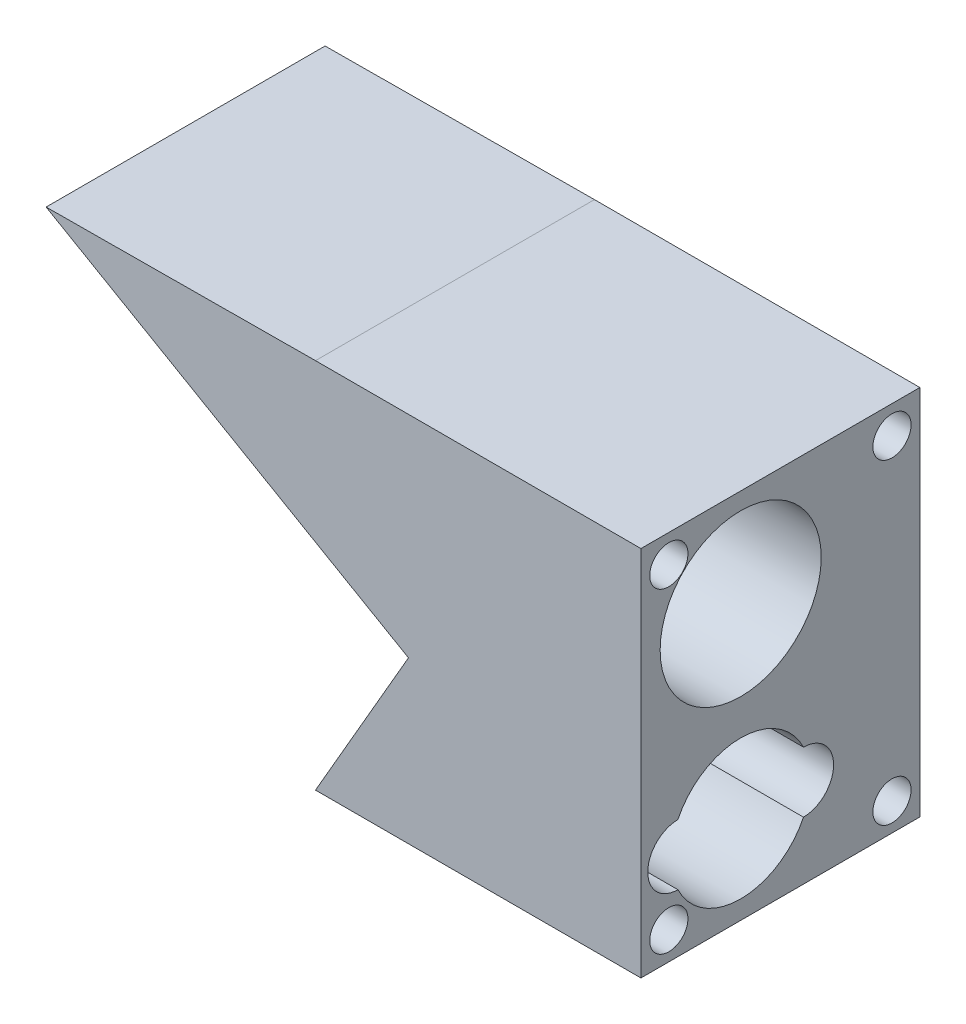
SolidWorks part; units mm, degrees
ref_plane "Front Plane" through (0, 0, 0) normal (0, 0, 1) x (1, 0, 0)
ref_plane "Top Plane" through (0, 0, 0) normal (0, 1, 0) x (1, 0, 0)
ref_plane "Right Plane" through (0, 0, 0) normal (1, 0, 0) x (0, 0, -1)
sketch "Sketch2" plane through (0, 0, 0) normal (0, 0, 1) x (1, 0, 0)
  line L1 (-40.5201, 26.3548) -> (3.9299, 26.3548)
  line L2 (-40.5201, 26.3548) -> (-40.5201, -24.4452)
  line L3 (-40.5201, -24.4452) -> (3.9299, -24.4452)
  line L4 (3.9299, 26.3548) -> (3.9299, -24.4452)
  dimension "D1" = 44.45
  dimension "D2" = 50.8
extrude "Boss-Extrude2" add sketch "Sketch2" along normal blind 38.1
hole_wizard "#5 (0.2055) Diameter Hole1" positions "3DSketch1" profile "Sketch4" hole size "#5" standard "ANSI Inch"
sketch3d "3DSketch1"
  line L0 (3.9299, 26.3548, 19.05) -> (3.9299, -24.4452, 19.05) construction
  line L1 (3.9299, 26.3548, 38.1) -> (3.9299, 26.3548, 0) construction
  line L2 (3.9299, -24.4452, 38.1) -> (3.9299, -24.4452, 0) construction
  line L4 (3.9299, 0.9548, 38.1) -> (3.9299, 0.9548, 0) construction
  line L5 (3.9299, -24.4452, 38.1) -> (3.9299, 26.3548, 38.1) construction
  line L6 (3.9299, -24.4452, 0) -> (3.9299, 26.3548, 0) construction
  point P0 (3.9299, 22.5448, 34.29)
  point P33 (3.9299, 22.5448, 3.81)
  point P35 (3.9299, -20.6352, 3.81)
  point P37 (3.9299, -20.6352, 34.29)
  dimension "D1" = 3.81
  dimension "D2" = 3.81
  dimension "D3" = 3.81
  dimension "D4" = 3.81
  dimension "D5" = 3.81
  dimension "D6" = 3.81
  dimension "D7" = 3.81
  dimension "D8" = 3.81
sketch "Sketch4" plane through (3.9299, 22.5448, 34.29) normal (0, 1, 0) x (0, 0, -1)
  line L0 (0, 0) -> (0, 14.2682)
  line L1 (0, 14.2682) -> (2.6098, 12.7)
  line L2 (2.6098, 12.7) -> (2.6098, 0)
  line L5 (2.6098, 0) -> (0, 0)
  line L10 (0, 14.2682) -> (-2.6099, 12.7) construction
  line L11 (0, -6.35) -> (0, 107.95) construction
  dimension "Hole Dia." = 5.2197
  dimension "Hole Depth" = 12.7
  dimension "Drill Angle" = 118
sketch "Sketch6" plane through (0, 0, 0) normal (0, 0, -1) x (-1, 0, 0)
  line L0 (40.5201, 26.3548) -> (77.3134, 26.1268)
  line L1 (77.3134, 26.1268) -> (40.5201, 4.8842)
  line L2 (40.5201, 26.3548) -> (40.5201, -24.4452) construction
  line L3 (77.3134, 26.1268) -> (27.8201, -2.4482) construction
  line L4 (40.5201, 4.8842) -> (40.5201, 26.3548)
extrude "Boss-Extrude3" add sketch "Sketch6" against normal blind 38.1
sketch "Sketch7" plane through (0, 0, 0) normal (0, 0, -1) x (-1, 0, 0)
  line L0 (40.5201, 4.8842) -> (27.8201, -2.4482)
  line L1 (27.8201, -2.4482) -> (40.5201, -24.4452)
  line L3 (40.5201, 4.8842) -> (77.3134, 26.1268) construction
  line L4 (40.5201, -24.4452) -> (40.5201, 4.8842)
extrude "Cut-Extrude2" cut sketch "Sketch7" against normal through all
sketch "Sketch3" plane through (3.9299, 0, 0) normal (1, 0, 0) x (0, 0, -1)
  line L0 (-24.4764, 26.3548) -> (-24.4764, -24.4452) construction
  line L1 (-38.1, 26.3548) -> (0, 26.3548) construction
  line L3 (-38.1, 0.9548) -> (0, 0.9548) construction
  line L4 (-38.1, -24.4452) -> (-38.1, 26.3548) construction
  line L5 (0, -24.4452) -> (0, 26.3548) construction
  circle A0 centre (-24.4764, 13.0198) radius 11
  arc A1 (-33.0537, -16.5221) -> (-15.899, -16.5221) centre (-24.4764, -12.3802) ccw
  arc A2 (-33.0537, -16.5221) -> (-33.0537, -8.2383) centre (-33.0267, -12.3802) cw
  arc A3 (-15.899, -16.5221) -> (-15.899, -8.2383) centre (-15.926, -12.3802) ccw
  arc A4 (-15.899, -8.2383) -> (-33.0537, -8.2383) centre (-24.4764, -12.3802) ccw
  dimension "D1" = 13.335
  dimension "D2" = 25.4
  dimension "D3" = 19.05
extrude "Cut-Extrude1" cut sketch "Sketch3" against normal through all both and the other way through all
